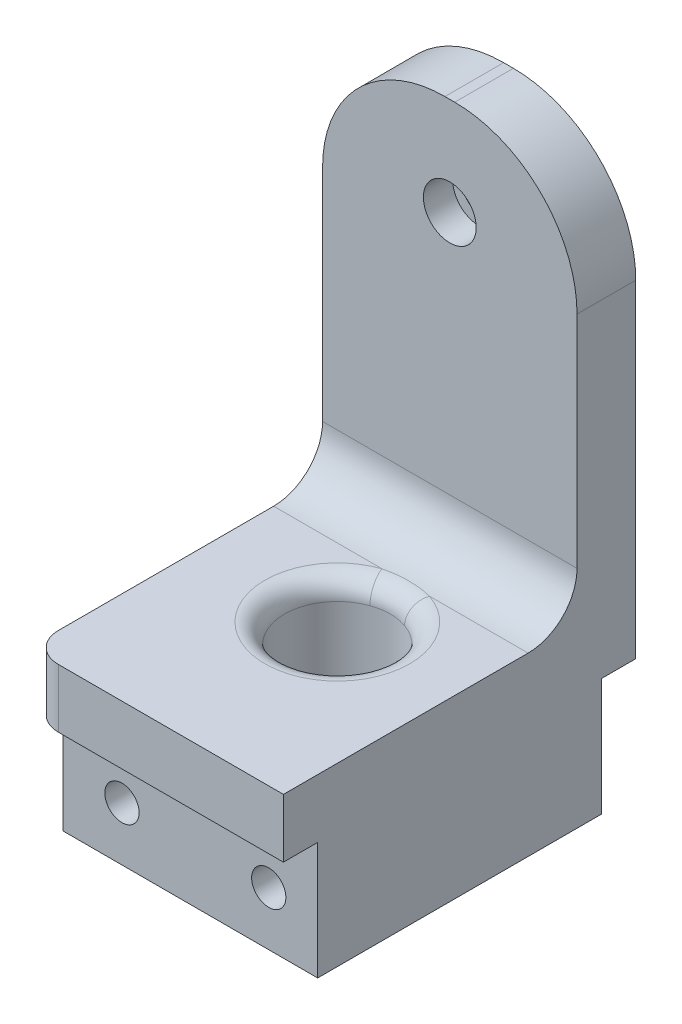
SolidWorks part; units mm, degrees
ref_plane "Front Plane" through (0, 0, 0) normal (0, 0, 1) x (1, 0, 0)
ref_plane "Top Plane" through (0, 0, 0) normal (0, 1, 0) x (1, 0, 0)
ref_plane "Right Plane" through (0, 0, 0) normal (1, 0, 0) x (0, 0, -1)
sketch "Sketch1" plane through (0, -44, 0) normal (0, 1, 0) x (1, 0, 0)
  line L0 (50.2641, 25) -> (50.2641, 28) construction
  line L1 (50.2641, -8) -> (50.2641, 28)
  line L2 (50.2641, -8) -> (27.2641, -8) construction
  line L3 (50.2641, -8) -> (27.2641, -8)
  line L4 (24.2641, -5) -> (24.2641, 25)
  line L5 (27.2641, 28) -> (50.2641, 28)
  arc A0 (27.2641, 28) -> (24.2641, 25) centre (27.2641, 25) ccw construction
  arc A1 (24.2641, -5) -> (27.2641, -8) centre (27.2641, -5) ccw construction
  arc A2 (27.2641, 28) -> (24.2641, 25) centre (27.2641, 25) ccw
  arc A3 (24.2641, -5) -> (27.2641, -8) centre (27.2641, -5) ccw
extrude "Boss-Extrude1" add sketch "Sketch1" along normal blind 6
sketch "Sketch2" plane through (0, -38, 0) normal (0, 1, 0) x (1, 0, 0)
  line L0 (24.2641, 25) -> (24.2641, -5) construction
  line L1 (50.2641, 28) -> (24.2641, 28)
  line L2 (50.2641, 28) -> (50.2641, 22)
  line L3 (50.2641, 22) -> (24.2641, 22)
  line L4 (24.2641, 28) -> (24.2641, 22)
  dimension "D1" = 6
extrude "Boss-Extrude2" add sketch "Sketch2" along normal blind 40
fillet "Fillet1" radius 12.5 2 edges at (24.2641, 2, -25) (50.2641, 2, -25)
sketch "Sketch3" plane through (0, 0, -22) normal (0, 0, 1) x (1, 0, 0)
  circle A0 centre (37.2641, -8) radius 2.7
extrude "Cut-Extrude1" cut sketch "Sketch3" against normal through all
sketch "Sketch4" plane through (0, -44, 0) normal (0, -1, 0) x (1, 0, 0)
  line L0 (24.2641, 5) -> (24.2641, -25) construction
  line L2 (24.2641, 4.5) -> (24.2641, -24.5)
  line L3 (50.2641, 4.5) -> (50.2641, -24.5)
  line L5 (24.2641, -25) -> (50.2641, -25) construction
  line L6 (50.2641, -24.5) -> (24.2641, -24.5)
  line L8 (24.2641, 4.5) -> (50.2641, 4.5)
  line L9 (50.2641, 5) -> (24.2641, 5) construction
  point P2 (23.4988, -24.85)
  point P3 (22.9876, 4.85)
  dimension "D1" = 0.5
  dimension "D2" = 0.5
extrude "Boss-Extrude3" add sketch "Sketch4" along normal blind 12
fillet "Fillet2" radius 5 1 edges at (37.2641, -38, -22)
sketch "Sketch5" plane through (0, 0, -24.5) normal (0, 0, -1) x (-1, 0, 0)
  circle A0 centre (-45.2641, -50.5) radius 1.75
  circle A1 centre (-30.2641, -50.5) radius 1.75
extrude "Cut-Extrude2" cut sketch "Sketch5" against normal through all
sketch "Sketch6" plane through (0, -38, 0) normal (0, -1, 0) x (1, 0, 0)
  line L2 (24.2641, -28) -> (27.2641, -28)
  line L3 (24.2641, -25) -> (24.2641, -28)
  line L4 (24.2641, -28) -> (27.2641, -28)
  line L5 (24.2641, -25) -> (24.2641, -28)
  arc A1 (24.2641, -25) -> (27.2641, -28) centre (27.2641, -25) ccw
  arc A2 (24.2641, -25) -> (27.2641, -28) centre (27.2641, -25) ccw
  dimension "D1" = 0
extrude "Cut-Extrude3" cut sketch "Sketch6" against normal through all
sketch "Sketch7" plane through (0, -56, 0) normal (0, -1, 0) x (1, 0, 0)
  line L0 (32.0141, 4.5) -> (28.5141, 4.5) construction
  line L1 (47.0141, 4.5) -> (43.5141, 4.5) construction
  line L2 (32.0141, 4.5) -> (28.5141, 4.5) construction
  line L3 (47.0141, 4.5) -> (43.5141, 4.5) construction
  line L4 (28.5141, 4.5) -> (28.5141, -10.0084) construction
  line L5 (47.0141, 4.5) -> (47.0141, -10.0084) construction
  line L6 (28.5141, -10.0084) -> (47.0141, -10.0084) construction
  circle A0 centre (37.7641, -10.0084) radius 5.4
extrude "Cut-Extrude4" cut sketch "Sketch7" against normal up to surface (18 mm away) up to face at (35.1398, -38, -2.4757)
fillet "Fillet3" radius 2 2 edges at (43.1641, -56, -10.0084) (32.3641, -38, -10.0084)
sketch "Sketch8" plane through (0, 0, -28) normal (0, 0, -1) x (-1, 0, 0)
  circle A0 centre (-37.2641, -8) radius 2.7 construction
  circle A1 centre (-37.2641, -8) radius 2.7
  circle A2 centre (-37.2641, -8) radius 1.6
extrude "Boss-Extrude4" add sketch "Sketch8" against normal blind 3
